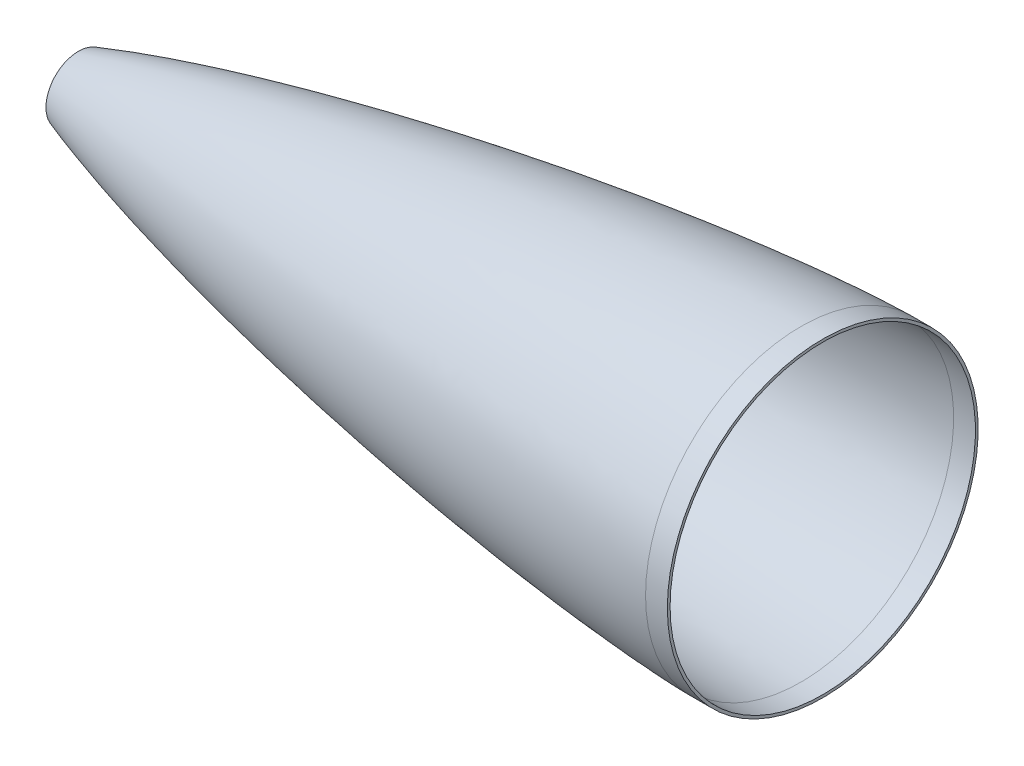
SolidWorks part; units mm, degrees
material "A-Glass Fiber"
ref_plane "Front Plane" through (0, 0, 0) normal (0, 0, 1) x (1, 0, 0)
ref_plane "Top Plane" through (0, 0, 0) normal (0, 1, 0) x (1, 0, 0)
ref_plane "Right Plane" through (0, 0, 0) normal (1, 0, 0) x (0, 0, -1)
sketch "Sketch1" plane through (0, 0, 0) normal (0, 0, 1) x (1, 0, 0)
  line L0 (0, 0) -> (457.2, 0) construction
  line L2 (457.2, 88.9) -> (457.2, 0) construction
  line L5 (457.2, 0) -> (469.8965, 0)
  line L7 (457.2, 88.9) -> (469.8965, 88.9)
  line L8 (469.8965, 0) -> (469.8965, 88.9) construction
  line L12 (457.1965, 90.4875) -> (471.484, 90.4875) construction
  line L13 (457.1965, 90.4875) -> (469.8965, 90.4875)
  line L14 (469.8965, 90.4875) -> (469.8965, 88.9)
  line L15 (457.2, 0) -> (-1.6168, 0) construction
  line L16 (471.484, -1.5875) -> (471.484, 90.4875) construction
  line L17 (457.2, 0) -> (0, 0) construction
  line L18 (457.2, -1.5875) -> (-1.923, -1.5875) construction
  line L19 (457.2, -1.5875) -> (471.484, -1.5875) construction
  line L20 (-1.6168, 0) -> (0, 0)
  spline S0 degree 4 poles (0, 0) (0.0023, 0.0117) (0.0082, 0.0346) (0.0259, 0.0787) (0.0695, 0.163) (0.1339, 0.2631) (0.2191, 0.3779) (0.337, 0.5207) (0.5083, 0.7099) (0.7967, 0.9963) (1.2974, 1.437) (2.1714, 2.1155) (3.7007, 3.1561) (6.4159, 4.7683) (11.1362, 7.1982) (18.8825, 10.6592) (32.1618, 15.8286) (51.2292, 22.2419) (75.2304, 29.3379) (102.9883, 36.6578) (131.6198, 43.512) (160.3745, 49.8273) (189.2277, 55.6742) (218.164, 61.0945) (247.1725, 66.1133) (276.2458, 70.7417) (305.3786, 74.9797) (334.5673, 78.8147) (363.8094, 82.22) (389.4419, 84.7797) (411.4452, 86.618) (428.6335, 87.7745) (439.7385, 88.3707) (448.4263, 88.7187) (453.4393, 88.8519) (455.9463, 88.8945) (457.2, 88.9) knots 0 0 0 0 0 0.000101 0.000202 0.000405 0.000809 0.001116 0.001422 0.001985 0.002988 0.004584 0.007113 0.011426 0.01877 0.031526 0.052412 0.083828 0.140383 0.203215 0.266046 0.328877 0.391708 0.454539 0.51737 0.580202 0.643033 0.705864 0.768695 0.831526 0.894357 0.925773 0.957189 0.978594 0.989297 1 1 1 1 1 construction
  spline S1 degree 4 poles (0, 0) (0.0023, 0.0117) (0.0082, 0.0346) (0.0259, 0.0787) (0.0695, 0.163) (0.1339, 0.2631) (0.2191, 0.3779) (0.337, 0.5207) (0.5083, 0.7099) (0.7967, 0.9963) (1.2974, 1.437) (2.1714, 2.1155) (3.7007, 3.1561) (6.4159, 4.7683) (11.1362, 7.1982) (18.8825, 10.6592) (32.1618, 15.8286) (51.2292, 22.2419) (75.2304, 29.3379) (102.9883, 36.6578) (131.6198, 43.512) (160.3745, 49.8273) (189.2277, 55.6742) (218.164, 61.0945) (247.1725, 66.1133) (276.2458, 70.7417) (305.3786, 74.9797) (334.5673, 78.8147) (363.8094, 82.22) (389.4419, 84.7797) (411.4452, 86.618) (428.6335, 87.7745) (439.7385, 88.3707) (448.4263, 88.7187) (453.4393, 88.8519) (455.9463, 88.8945) (457.2, 88.9) knots 0 0 0 0 0 0.000101 0.000202 0.000405 0.000809 0.001116 0.001422 0.001985 0.002988 0.004584 0.007113 0.011426 0.01877 0.031526 0.052412 0.083828 0.140383 0.203215 0.266046 0.328877 0.391708 0.454539 0.51737 0.580202 0.643033 0.705864 0.768695 0.831526 0.894357 0.925773 0.957189 0.978594 0.989297 1 1 1 1 1
  spline S2 degree 1 poles (-1.923, -1.5875) (457.1965, 90.4875) knots 0 0 1 1 construction
  spline S3 degree 3 poles (-1.923, -1.5875) (-1.8939, -1.4366) (-1.8357, -1.1349) (-1.7629, -0.7577) (-1.7047, -0.4559) (-1.6683, -0.2673) (-1.6392, -0.1164) (-1.6174, -0.0032) (-1.5992, 0.0909) (-1.5846, 0.1668) (-1.5757, 0.2128) (-1.568, 0.2528) (-1.5646, 0.2707) (-1.5593, 0.2973) (-1.5609, 0.2905) (-1.535, 0.4181) (-1.4945, 0.5502) (-1.4375, 0.695) (-1.3857, 0.8054) (-1.3028, 0.9624) (-1.2004, 1.1235) (-1.0488, 1.336) (-0.8721, 1.551) (-0.6674, 1.7754) (-0.4664, 1.9786) (-0.2007, 2.2308) (0.1296, 2.5208) (0.5253, 2.8433) (1.0549, 3.2501) (1.7196, 3.7245) (2.524, 4.259) (3.6029, 4.9361) (4.9652, 5.7326) (7.1644, 6.9318) (9.9467, 8.3264) (13.3187, 9.8899) (17.8521, 11.8645) (23.5695, 14.1711) (30.4875, 16.7597) (37.4467, 19.211) (44.4398, 21.5506) (53.8002, 24.5438) (65.5559, 28.0861) (79.7302, 32.0851) (93.9576, 35.8745) (108.2289, 39.484) (122.5371, 42.9348) (141.6579, 47.3445) (165.6299, 52.5284) (194.4886, 58.2899) (223.4264, 63.6303) (252.4339, 68.5723) (281.5049, 73.1249) (310.6349, 77.2859) (339.8213, 81.0405) (369.0631, 84.3576) (393.4776, 86.7119) (413.0398, 88.2952) (427.7267, 89.3064) (439.9858, 89.9745) (449.798, 90.3482) (454.7322, 90.4766) (457.1965, 90.4875) knots -0.00409 -0.00409 -0.00409 -0.00409 -0.00311 -0.002129 -0.001639 -0.001149 -0.000904 -0.000658 -0.000413 -0.000291 -0.000168 -0.000107 -0.000046 -0.000015 0 0.000016 0.000077 0.000138 0.0002 0.000322 0.000567 0.000812 0.001303 0.001793 0.002283 0.002774 0.003754 0.004735 0.005715 0.007676 0.009638 0.011599 0.015521 0.019443 0.027288 0.035132 0.042977 0.058666 0.074355 0.090044 0.105733 0.121422 0.1528 0.184178 0.215556 0.246934 0.278312 0.30969 0.372446 0.435202 0.497959 0.560715 0.623471 0.686227 0.748983 0.811739 0.874495 0.905873 0.937251 0.968629 0.984318 1.000007 1.000007 1.000007 1.000007 only from (-1.6168, 0) to (457.1965, 90.4875)
  dimension "D1" = 457.2
  dimension "D3" = 12.7
  dimension "D4" = 1.5875
revolve "Revolve3" add sketch "Sketch1" angle 360 about L0
ref_plane "Plane1" through (-1.6168, 0, 0) normal (1, 0, 0) x (0, 0, -1)
sketch "Sketch2" plane through (-1.6168, 0, 0) normal (1, 0, 0) x (0, 0, -1)
  circle A0 centre (0, 0) radius 90.4875 construction
  circle A1 centre (0, 0) radius 90.4875
extrude "Cut-Extrude1" cut sketch "Sketch2" along normal blind 38.1
